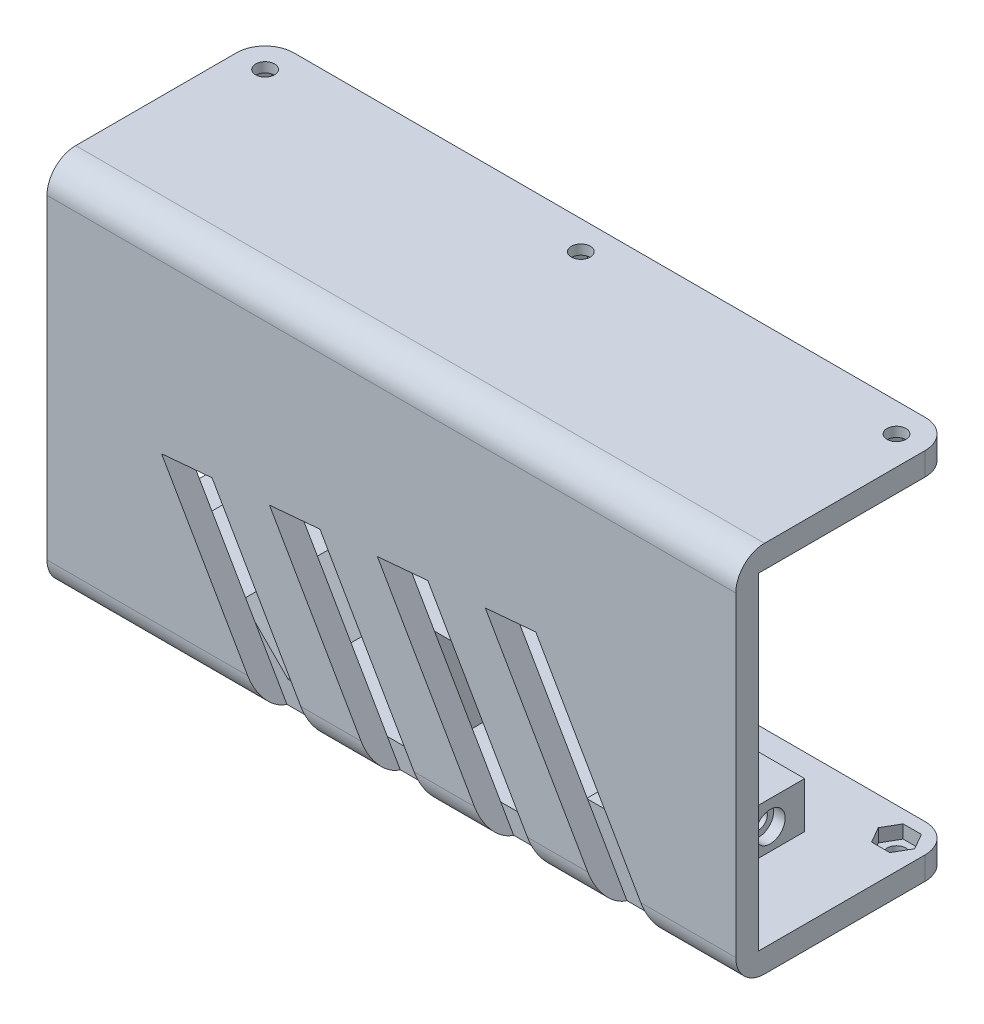
SolidWorks part; units mm, degrees
ref_plane "Front Plane" through (0, 0, 0) normal (0, 0, 1) x (1, 0, 0)
ref_plane "Top Plane" through (0, 0, 0) normal (0, 1, 0) x (1, 0, 0)
ref_plane "Right Plane" through (0, 0, 0) normal (1, 0, 0) x (0, 0, -1)
sketch "Sketch2" plane through (0, 0, 0) normal (0, 0, 1) x (1, 0, 0)
  line L1 (0, 0) -> (120, 0)
  line L2 (0, 0) -> (0, 65)
  line L3 (0, 65) -> (120, 65)
  line L4 (120, 0) -> (120, 65)
  dimension "D1" = 120
  dimension "D2" = 65
extrude "Boss-Extrude1" add sketch "Sketch2" along normal blind 38
sketch "Sketch3" plane through (0, 0, 38) normal (0, 0, 1) x (1, 0, 0)
  line L0 (106, 53) -> (106, 61)
  line L1 (92, 53) -> (106, 53)
  line L3 (92, 12) -> (106, 12)
  line L4 (106, 53) -> (106, 12)
  line L5 (106, 61) -> (120, 61)
  line L6 (120, 0) -> (120, 65) construction
  line L7 (106, 12) -> (106, 4)
  line L8 (106, 4) -> (120, 4)
  line L9 (120, 61) -> (120, 4)
  line L10 (120, 0) -> (120, 65)
  line L11 (60, 65) -> (60, 0) construction
  line L12 (120, 65) -> (0, 65) construction
  line L13 (0, 61) -> (0, 4)
  line L14 (14, 4) -> (0, 4)
  line L15 (14, 12) -> (14, 4)
  line L16 (14, 61) -> (0, 61)
  line L17 (14, 53) -> (14, 12)
  line L18 (28, 12) -> (14, 12)
  line L19 (28, 12) -> (28, 4)
  line L20 (28, 53) -> (14, 53)
  line L21 (14, 53) -> (14, 61)
  line L22 (28, 4) -> (92, 4)
  line L24 (28, 53) -> (28, 61)
  line L25 (28, 61) -> (92, 61)
  line L26 (92, 61) -> (92, 53)
  line L27 (92, 4) -> (92, 12)
  point P9 (120, 32.5)
  point P11 (120, 32.5)
  line M9 (0, 65) -> (0, 0)
  line M11 (120, 0) -> (120, 65)
  dimension "D1" = 41
  dimension "D2" = 14
  dimension "D3" = 8
  dimension "D4" = 14
extrude "Cut-Extrude1" cut sketch "Sketch3" against normal offset from surface (34 mm away) 4 contours L17 L21 L16 L14 L15 M9 | L11 L25 L24 L20 L17 L18 L19 L22 | L25 L11 L22 L27 L3 L4 L1 L26 | L7 L8 L5 L0 L4 M11 region at (81.5054, 32.5, 38) region at (113, 32.5, 38) region at (38.4946, 32.5, 38) region at (7, 32.5, 38) up to face at (60, 32.5, 0)
fillet "Fillet1" radius 5 2 edges at (60, 0, 0) (60, 65, 0)
sketch "Sketch4" plane through (0, 0, 38) normal (0, 0, 1) x (1, 0, 0)
  line L1 (0, 61) -> (120, 61)
  line L2 (0, 61) -> (0, 4)
  line L3 (0, 4) -> (120, 4)
  line L4 (120, 61) -> (120, 4)
extrude "Cut-Extrude2" cut sketch "Sketch4" against normal offset from surface (12 mm away) 22 up to face at (60, 32.5, 4)
fillet "Fillet2" radius 5 4 edges at (0, 2, 38) (120, 2, 38) (120, 63, 38) (0, 63, 38)
chamfer "Chamfer1" distance 10 angle 45 4 edges at (92, 4, 15) (92, 61, 15) (28, 61, 15) (28, 4, 15)
ref_plane "Plane1" through (60, 0, 0) normal (-1, 0, 0) x (0, 0, 1)
sketch "Sketch8" plane through (0, 61, 0) normal (0, -1, 0) x (1, 0, 0)
  line L0 (5, 33) -> (115, 33) construction
  line L9 (8.1754, 33) -> (6.5877, 35.75)
  line L10 (6.5877, 35.75) -> (3.4123, 35.75)
  line L11 (3.4123, 35.75) -> (1.8246, 33)
  line L12 (1.8246, 33) -> (3.4123, 30.25)
  line L13 (3.4123, 30.25) -> (6.5877, 30.25)
  line L14 (6.5877, 30.25) -> (8.1754, 33)
  line L15 (118.1754, 33) -> (116.5877, 35.75)
  line L16 (116.5877, 35.75) -> (113.4123, 35.75)
  line L17 (113.4123, 35.75) -> (111.8246, 33)
  line L18 (111.8246, 33) -> (113.4123, 30.25)
  line L19 (113.4123, 30.25) -> (116.5877, 30.25)
  line L20 (116.5877, 30.25) -> (118.1754, 33)
  line L21 (63.1754, 33) -> (61.5877, 35.75)
  line L22 (61.5877, 35.75) -> (58.4123, 35.75)
  line L23 (58.4123, 35.75) -> (56.8246, 33)
  line L24 (56.8246, 33) -> (58.4123, 30.25)
  line L25 (58.4123, 30.25) -> (61.5877, 30.25)
  line L26 (61.5877, 30.25) -> (63.1754, 33)
  circle A0 centre (5, 33) radius 2.75 construction
  circle A1 centre (115, 33) radius 2.75 construction
  circle A2 centre (60, 33) radius 2.75 construction
  circle A3 centre (5, 33) radius 1.65
  circle A4 centre (60, 33) radius 1.65
  circle A5 centre (115, 33) radius 1.65
  point P20 (5, 30.25)
  dimension "D4" = 3.3
  dimension "D1" = 5.5
  dimension "D2" = 5.5
  dimension "D3" = 5.5
extrude "Cut-Extrude4" cut sketch "Sketch8<2>" against normal through all contours A3 | A4 | A5 region at (5, 61, 33) region at (60, 61, 33) region at (115, 61, 33)
sketch "Sketch8<2>" plane through (0, 61, 0) normal (0, -1, 0) x (1, 0, 0) same geometry as "Sketch8"
extrude "Cut-Extrude3" cut sketch "Sketch8" against normal blind 2.3
ref_plane "Plane2" through (0, 32.5, 0) normal (0, 1, 0) x (1, 0, 0)
mirror "Mirror1" about plane through (0, 32.5, 0) normal (0, 1, 0) of "Cut-Extrude4", "Cut-Extrude3"
sketch "Sketch10" plane through (106, 0, 0) normal (1, 0, 0) x (0, 0, -1)
  line L0 (-15, 57.25) -> (-15, 7.75) construction
  line L1 (-15, 12) -> (-15, 53) construction
  line L2 (-4, 12) -> (-26, 12) construction
  line L3 (-4, 53) -> (-26, 53) construction
  line L5 (-20, 57.25) -> (-10, 57.25) construction
  line L6 (-20, 7.75) -> (-10, 7.75) construction
  circle A0 centre (-20, 57.25) radius 1.5
  circle A1 centre (-10, 57.25) radius 1.5
  circle A2 centre (-10, 7.75) radius 1.5
  circle A3 centre (-20, 7.75) radius 1.5
  point P8 (-15, 57.25)
  point P11 (-15, 32.5)
  point P12 (-15, 32.5)
  point P15 (-15, 7.75)
  dimension "D4" = 3
  dimension "D1" = 49.5
  dimension "D2" = 10
  dimension "D3" = 10
extrude "Cut-Extrude5" cut sketch "Sketch10" against normal through all
sketch "Sketch6" plane through (60, 0, 0) normal (-1, 0, 0) x (0, 0, 1)
  line L0 (4, 41) -> (24, 61)
  line L2 (4, 61) -> (33, 61) construction
  line L3 (4, 24) -> (24, 4)
  line L4 (4, 4) -> (26, 4) construction
  line L5 (4, 41) -> (4, 61)
  line L6 (4, 61) -> (24, 61)
  line L7 (4, 24) -> (4, 4)
  line L8 (4, 4) -> (24, 4)
  line L9 (4, 61) -> (4, 4) construction
  dimension "D1" = 45
  dimension "D2" = 45
  dimension "D3" = 20
  dimension "D4" = 20
extrude "Boss-Extrude2" add sketch "Sketch6" along normal blind 1.5 and the other way blind 1.5 contours L7 L8 L3 | L0 L6 L5 region at (60, 10.6667, 10.6667)
sketch "Sketch11" plane through (106, 0, 0) normal (1, 0, 0) x (0, 0, -1)
  circle A0 centre (-20, 57.25) radius 2.6
  circle A1 centre (-10, 57.25) radius 2.6
  circle A2 centre (-10, 7.75) radius 2.6
  circle A3 centre (-20, 7.75) radius 2.6
  dimension "D1" = 5.2
extrude "Cut-Extrude6" cut sketch "Sketch11" against normal blind 2
mirror "Mirror2" about plane through (60, 0, 0) normal (-1, 0, 0) of "Cut-Extrude6"
sketch "Sketch12" plane through (0, 0, 0) normal (0, 0, -1) x (-1, 0, 0)
  line L0 (-106.3398, 0) -> (-85.154, 36.695)
  line L1 (0, 0) -> (-120, 0) construction
  line L3 (-76.3605, 35.9257) -> (-97.1022, 0)
  line L4 (-97.1022, 0) -> (-106.3398, 0)
  line L5 (-86.5913, 0) -> (-66.355, 35.0503)
  line L7 (-57.5616, 34.281) -> (-77.3537, 0)
  line L8 (-77.3537, 0) -> (-86.5913, 0)
  line L9 (-66.8428, 0) -> (-47.5561, 33.4056)
  line L11 (-38.7627, 32.6363) -> (-57.6052, 0)
  line L12 (-57.6052, 0) -> (-66.8428, 0)
  line L13 (-47.0943, 0) -> (-28.7572, 31.7609)
  line L15 (-19.9638, 30.9916) -> (-37.8567, 0)
  line L16 (-37.8567, 0) -> (-47.0943, 0)
  line L17 (-85.154, 36.695) -> (-76.3605, 35.9257)
  line L18 (-28.7572, 31.7609) -> (-19.9638, 30.9916)
  line L19 (-47.5561, 33.4056) -> (-38.7627, 32.6363)
  line L20 (-66.355, 35.0503) -> (-57.5616, 34.281)
  line L21 (-85.154, 36.695) -> (-67.3568, 36.695) construction
  dimension "D1" = 8
  dimension "D2" = 60
  dimension "D4" = 5
  dimension "D3" = 4
extrude "Cut-Extrude7" cut sketch "Sketch12" against normal up to surface (4 mm away) up to face at (60, 32.5, 4)
mirror "Mirror4" about plane through (0, 0, 0) normal (0, 0, 1) of bodies 111
delete or keep bodies "Body-Delete/Keep 1" type delete bodies bodies 111
